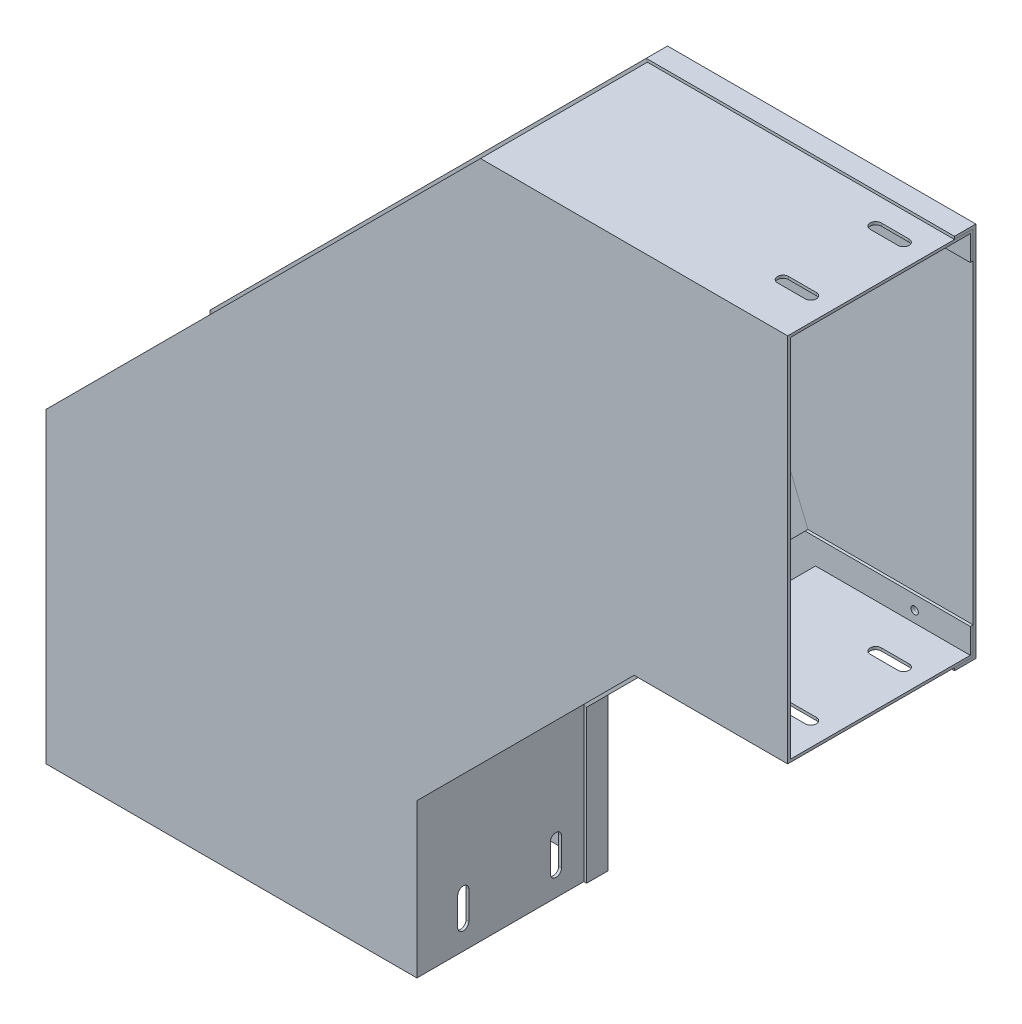
SolidWorks part; units mm, degrees
material "Plain Carbon Steel"
ref_plane "Front Plane" through (0, 0, 0) normal (0, 0, 1) x (1, 0, 0)
ref_plane "Top Plane" through (0, 0, 0) normal (0, 1, 0) x (1, 0, 0)
ref_plane "Right Plane" through (0, 0, 0) normal (1, 0, 0) x (0, 0, -1)
sketch "ElbowArc" plane through (0, 0, 0) normal (0, 0, 1) x (1, 0, 0)
  line L2 (-300, 0) -> (-300, 124.2641)
  line L3 (-300, 124.2641) -> (-124.2641, 300)
  line L4 (-124.2641, 300) -> (0, 300)
  arc A0 (-300, 0) -> (0, 300) centre (0, 0) cw construction
  dimension "BendRadius" = 300
  dimension "BendAngle" = 90
sketch "Sketch1" plane through (0, 0, 0) normal (0, 1, 0) x (1, 0, 0)
  line L0 (-300, 0) -> (203.1914, 0) construction
  line L1 (-200, -50) -> (-400, -50)
  line L2 (-400, -50) -> (-400, 50)
  line L3 (-200, -50) -> (-200, 50)
  line L4 (-398.5, -48.5) -> (-398.5, 48.5)
  line L5 (-201.5, -48.5) -> (-398.5, -48.5)
  line L6 (-201.5, -48.5) -> (-201.5, 48.5)
  line L7 (-400, 50) -> (-385, 50)
  line L8 (-385, 48.5) -> (-398.5, 48.5)
  line L9 (-200, 50) -> (-400, -50) construction
  line L10 (-385, 48.5) -> (-385, 50)
  line L11 (-200, 50) -> (-215, 50)
  line L12 (-398.5, -48.5) -> (-398.5, 50) construction
  line L13 (-215, 50) -> (-215, 48.5)
  line L14 (-215, 48.5) -> (-201.5, 48.5)
  line L16 (-201.5, -48.5) -> (-201.5, 50) construction
  dimension "D2" = 15
  dimension "Width" = 200
  dimension "AlignmentAngle" = 0
  dimension "Height" = 100
  dimension "D1" = 1.5
  dimension "Thickness" = 1.5
sweep "Sweep1" add profiles "Sketch1" path "ElbowArc"
ref_plane "Plane1" through (-300, 0, 0) normal (1, 0, 0) x (0, 1, 0)
sketch "Sketch2" plane through (-300, 0, 0) normal (1, 0, 0) x (0, 0, -1)
  line L0 (-50, 20) -> (0, 20) construction
  line L2 (0, 20) -> (50, 20) construction
  line L3 (0, 0) -> (0, 40) construction
  line L7 (-25, 12.5) -> (-25, 27.5) construction
  line L8 (-28, 12.5) -> (-28, 27.5)
  line L9 (-22, 12.5) -> (-22, 27.5)
  line L10 (25, 12.5) -> (25, 27.5) construction
  line L11 (22, 12.5) -> (22, 27.5)
  line L12 (28, 12.5) -> (28, 27.5)
  line L13 (0, 0) -> (0, 124.2641) construction
  arc A0 (-28, 12.5) -> (-22, 12.5) centre (-25, 12.5) ccw
  arc A1 (-22, 27.5) -> (-28, 27.5) centre (-25, 27.5) ccw
  arc A2 (22, 12.5) -> (28, 12.5) centre (25, 12.5) ccw
  arc A3 (28, 27.5) -> (22, 27.5) centre (25, 27.5) ccw
  point P10 (-25, 20)
  point P16 (25, 20)
  dimension "D1" = 3
  dimension "D2" = 15
  dimension "D3" = 40
  dimension "D5" = 50
extrude "Cut-Extrude1" cut sketch "Sketch2" against normal through all and the other way through all
ref_plane "Plane2" through (0, 300, 0) normal (0, -1, 0) x (1, 0, 0)
sketch "Sketch3" plane through (0, 300, 0) normal (0, 1, 0) x (-1, 0, 0)
  line L0 (20, 0) -> (20, -50) construction
  line L4 (20, 0) -> (20, 50) construction
  line L6 (40, 0) -> (0, 0) construction
  line L7 (124.2641, 0) -> (0, 0) construction
  line L9 (12.5, 25) -> (27.5, 25) construction
  line L10 (12.5, 28) -> (27.5, 28)
  line L11 (12.5, 22) -> (27.5, 22)
  line L12 (12.5, -25) -> (27.5, -25) construction
  line L13 (12.5, -22) -> (27.5, -22)
  line L14 (12.5, -28) -> (27.5, -28)
  arc A0 (12.5, 28) -> (12.5, 22) centre (12.5, 25) ccw
  arc A1 (27.5, 22) -> (27.5, 28) centre (27.5, 25) ccw
  arc A2 (12.5, -22) -> (12.5, -28) centre (12.5, -25) ccw
  arc A3 (27.5, -28) -> (27.5, -22) centre (27.5, -25) ccw
  point P12 (20, 25)
  point P18 (20, -25)
  dimension "D1" = 3
  dimension "D2" = 15
  dimension "D3" = 40
  dimension "D5" = 50
extrude "Cut-Extrude2" cut sketch "Sketch3" against normal through all and the other way through all
ref_plane "Plane3" through (0, 0, 0) normal (0, 0, 1) x (0, 1, 0)
sketch "Sketch4" plane through (0, 0, 0) normal (0, 0, -1) x (-1, 0, 0)
  line L0 (200, 30) -> (400, 30) construction
  line L1 (300, 0) -> (300, 124.2641) construction
  circle A0 centre (392.5, 30) radius 2
  circle A1 centre (207.5, 30) radius 2
  point P6 (300, 30)
  dimension "D4" = 4
  dimension "D1" = 200
  dimension "D2" = 7.5
  dimension "D3" = 7.5
  dimension "D5" = 30
extrude "Cut-Extrude3" cut sketch "Sketch4" along normal through all
ref_plane "Plane4" through (0, 0, 0) normal (0, 0, 1) x (1, 0, 0)
sketch "Sketch5" plane through (0, 0, 0) normal (0, 0, 1) x (1, 0, 0)
  line L0 (-30, 400) -> (-30, 200) construction
  line L1 (-124.2641, 300) -> (0, 300) construction
  circle A0 centre (-30, 392.5) radius 2
  circle A1 centre (-30, 207.5) radius 2
  point P6 (-30, 300)
  dimension "D2" = 4
  dimension "D1" = 30
  dimension "D3" = 200
  dimension "D4" = 7.5
  dimension "D5" = 7.5
extrude "Cut-Extrude4" cut sketch "Sketch5" against normal up to next
sketch "Sketch8" plane through (0, 0, 0) normal (0, 1, 0) x (1, 0, 0)
  line L0 (-400, 40) -> (-400, 50)
  line L1 (-400, 50) -> (-200, 50)
  line L2 (-200, 50) -> (-200, 40)
  line L3 (-125.9212, 0) -> (-300, 0) construction
  line L4 (-300, 0) -> (203.1914, 0) construction
  line L5 (-401.5, 40) -> (-401.5, 51.5)
  line L6 (-401.5, 51.5) -> (-198.5, 51.5)
  line L7 (-198.5, 51.5) -> (-198.5, 40)
  line L8 (-198.5, 40) -> (-200, 40)
  line L9 (-400, 40) -> (-401.5, 40)
  line L10 (-300, 50) -> (-300, -50) construction
  line L11 (-201.5, -48.5) -> (-398.5, -48.5) construction
  point P8 (-300, 0)
  dimension "Thickness" = 1.5
  dimension "D2" = 200
  dimension "D3" = 10
  dimension "D1" = 100
sweep "Sweep2" add profiles "Sketch8" path "ElbowArc<2>"
sketch "ElbowArc<2>" plane through (0, 0, 0) normal (0, 0, 1) x (1, 0, 0) same geometry as "ElbowArc"
sketch "Sketch10" plane through (0, 0, 0) normal (0, 0, 1) x (0, 1, 0)
  circle A2 centre (30, 207.5) radius 2 construction
  circle A3 centre (30, 392.5) radius 2 construction
  circle A4 centre (30, 207.5) radius 2
  circle A5 centre (30, 392.5) radius 2
extrude "Cut-Extrude5" cut sketch "Sketch10" against normal through all
sketch "Sketch11" plane through (0, 0, 0) normal (0, 0, 1) x (1, 0, 0)
  circle A2 centre (-30, 207.5) radius 2 construction
  circle A3 centre (-30, 392.5) radius 2 construction
  circle A4 centre (-30, 207.5) radius 2
  circle A5 centre (-30, 392.5) radius 2
extrude "Cut-Extrude6" cut sketch "Sketch11" against normal through all
sketch "Sketch6" plane through (0, 0, 0) normal (0, 0, -1) x (-1, 0, 0)
  point P0 (300, 0)
  point P1 (0, 300)
other "CPoint1" parameters "Diameter"=10, "StubLength"=200
ref_axis "Axis2" through (10, 300, 0) along (-1, 0, 0)
other "CPoint2" parameters "Diameter"=10, "StubLength"=200
ref_axis "Axis3" through (-300, -10, 0) along (0, 1, 0)
equation "\"D5@Sketch3\"=\"Height@Sketch1\"/2"
equation "\"D5@Sketch2\"=\"Height@Sketch1\"/2"
equation "\"D1@Plane1\"=\"AlignmentAngle@Sketch1\""
equation "\"D1@Sketch1\"=\"Thickness@Sketch1\""
equation "\"D1@Sketch4\" = \"Width@Sketch1\""
equation "\"D1@Plane3\"=\"AlignmentAngle@Sketch1\""
equation "\"D1@Plane4\"=\"AlignmentAngle@Sketch1\""
equation "\"D3@Sketch5\" = \"Width@Sketch1\""
equation "\"D4@Sketch5\" = \"D2@Sketch1\" / 2"
equation "\"D5@Sketch5\" = \"D4@Sketch5\""
equation "\"D2@Sketch4\" = \"D2@Sketch1\" / 2"
equation "\"D3@Sketch4\" = \"D2@Sketch4\""
equation "\"D1@Sketch8\"=\"Height@Sketch1\""
equation "\"D2@Sketch8\"=\"Width@Sketch1\""
equation "\"Thickness@Sketch8\" = \"Thickness@Sketch1\""
